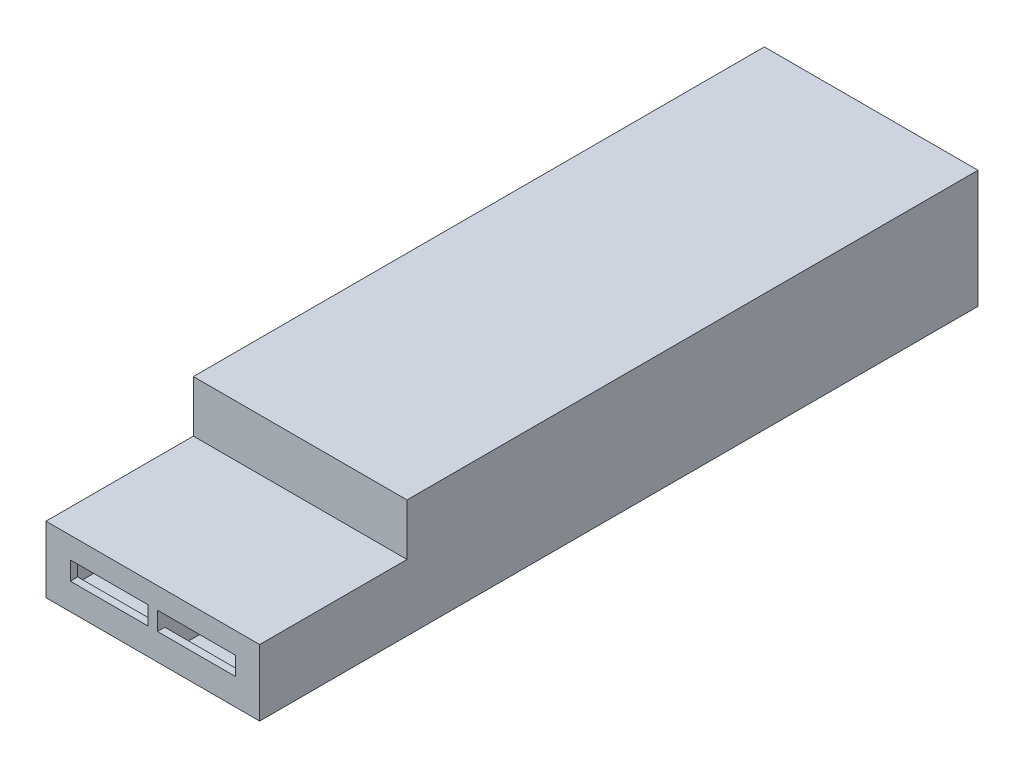
SolidWorks part; units mm, degrees
ref_plane "Front Plane" through (0, 0, 0) normal (0, 0, 1) x (1, 0, 0)
ref_plane "Top Plane" through (0, 0, 0) normal (0, 1, 0) x (1, 0, 0)
ref_plane "Right Plane" through (0, 0, 0) normal (1, 0, 0) x (0, 0, -1)
sketch "Sketch1" plane through (0, 0, 0) normal (0, 0, 1) x (1, 0, 0)
  line L0 (-22.4, 3.2) -> (-1.25, 3.2)
  line L1 (-29, 9) -> (29, 9)
  line L2 (-29, 9) -> (-29, -9)
  line L3 (-29, -9) -> (29, -9)
  line L4 (29, 9) -> (29, -9)
  line L5 (-29, 9) -> (29, -9) construction
  line L6 (-29, -9) -> (29, 9) construction
  line L7 (-22.4, -1.8) -> (-1.25, -1.8)
  line L8 (22.4, 3.2) -> (22.4, -1.8)
  line L9 (-22.4, 3.2) -> (-22.4, -1.8)
  line L10 (-1.25, 3.2) -> (-1.25, -1.8)
  line L11 (1.25, 3.2) -> (1.25, -1.8)
  line L12 (0, 0) -> (0, 24.1062) construction
  line L13 (-1.25, -1.8) -> (1.25, -1.8) construction
  line L14 (1.25, -1.8) -> (22.4, -1.8)
  line L15 (0, 3.2) -> (1.25, 3.2) construction
  line L16 (1.25, 3.2) -> (22.4, 3.2)
  line L17 (-1.25, 3.2) -> (0, 3.2) construction
  point P0 (0, 0)
  point P18 (-22.4, 0.7)
  point P19 (2.917, -1.8)
  point P20 (0, 0)
  point P21 (1.3582, -1.8)
  dimension "D1" = 18
  dimension "D2" = 58
  dimension "D3" = 5.8
  dimension "D4" = 7.2
  dimension "D5" = 44.8
  dimension "D6" = 2.5
  dimension "D7" = 6.6
extrude "Boss-Extrude1" add sketch "Sketch1" along normal blind 40
sketch "Sketch2" plane through (0, 0, 0) normal (0, 0, -1) x (-1, 0, 0)
  line L0 (29, 9) -> (29, -9) construction
  line L1 (-29, -9) -> (29, -9)
  line L2 (-29, -9) -> (-29, 23)
  line L3 (-29, 23) -> (29, 23)
  line L4 (29, -9) -> (29, 23)
  line L5 (29, -9) -> (-29, -9) construction
  point P4 (29, -9)
  dimension "D1" = 32
extrude "Boss-Extrude2" add sketch "Sketch2" along normal blind 155
sketch "Sketch3" plane through (0, 0, 40) normal (0, 0, -1) x (-1, 0, 0)
  line L1 (27.5, 8.25) -> (-27.5, 8.25)
  line L2 (27.5, 8.25) -> (27.5, -8.25)
  line L3 (27.5, -8.25) -> (-27.5, -8.25)
  line L4 (-27.5, 8.25) -> (-27.5, -8.25)
  line L5 (27.5, 8.25) -> (-27.5, -8.25) construction
  line L6 (27.5, -8.25) -> (-27.5, 8.25) construction
  point P0 (0, 0)
  dimension "D1" = 16.5
  dimension "D2" = 55
extrude "Cut-Extrude1" cut sketch "Sketch3" along normal blind 39 from offset 2
sketch "Sketch4" plane through (0, 0, 40) normal (0, 0, -1) x (-1, 0, 0)
  line L1 (1.25, 8.25) -> (-1.25, 8.25)
  line L2 (1.25, 8.25) -> (1.25, -8.25)
  line L3 (1.25, -8.25) -> (-1.25, -8.25)
  line L4 (-1.25, 8.25) -> (-1.25, -8.25)
  line L5 (1.25, 8.25) -> (-1.25, -8.25) construction
  line L6 (1.25, -8.25) -> (-1.25, 8.25) construction
  line L8 (-1.25, 3.2) -> (-1.25, -1.8) construction
  line L9 (-27.5, -8.25) -> (27.5, -8.25) construction
  point P0 (0, 0)
  point P10 (0, 0)
  point P11 (0, 0)
extrude "Boss-Extrude3" add sketch "Sketch4" along normal blind 20
fillet "Fillet1" radius 1.25 2 edges at (1.25, 0, 20) (-1.25, 0, 20)
sketch "Sketch5" plane through (0, 0, -155) normal (0, 0, -1) x (-1, 0, 0)
  line L1 (-27.5, -7.5) -> (27.5, -7.5)
  line L2 (-27.5, -7.5) -> (-27.5, 21.5)
  line L3 (-27.5, 21.5) -> (27.5, 21.5)
  line L4 (27.5, -7.5) -> (27.5, 21.5)
  line L5 (-27.5, -7.5) -> (27.5, 21.5) construction
  line L6 (-27.5, 21.5) -> (27.5, -7.5) construction
  line L7 (-29, -9) -> (29, -9) construction
  point P0 (0, 7)
  dimension "D1" = 55
  dimension "D2" = 29
  dimension "D3" = 1.5
extrude "Cut-Extrude2" cut sketch "Sketch5" against normal blind 153.5
sketch "Sketch6" plane through (0, 0, -1) normal (0, 0, 1) x (1, 0, 0)
  line L4 (27.5, -8.25) -> (27.5, 8.25)
  line L5 (27.5, 8.25) -> (-27.5, 8.25)
  line L6 (-27.5, 8.25) -> (-27.5, -8.25)
  line L7 (-27.5, -8.25) -> (27.5, -8.25)
  line L8 (27.5, -8.25) -> (27.5, 8.25)
  line L9 (27.5, 8.25) -> (-27.5, 8.25)
  line L10 (-27.5, 8.25) -> (-27.5, -8.25)
  line L11 (-27.5, -8.25) -> (27.5, -8.25)
  dimension "D1" = 0
extrude "Cut-Extrude3" cut sketch "Sketch6" against normal blind 153.5
